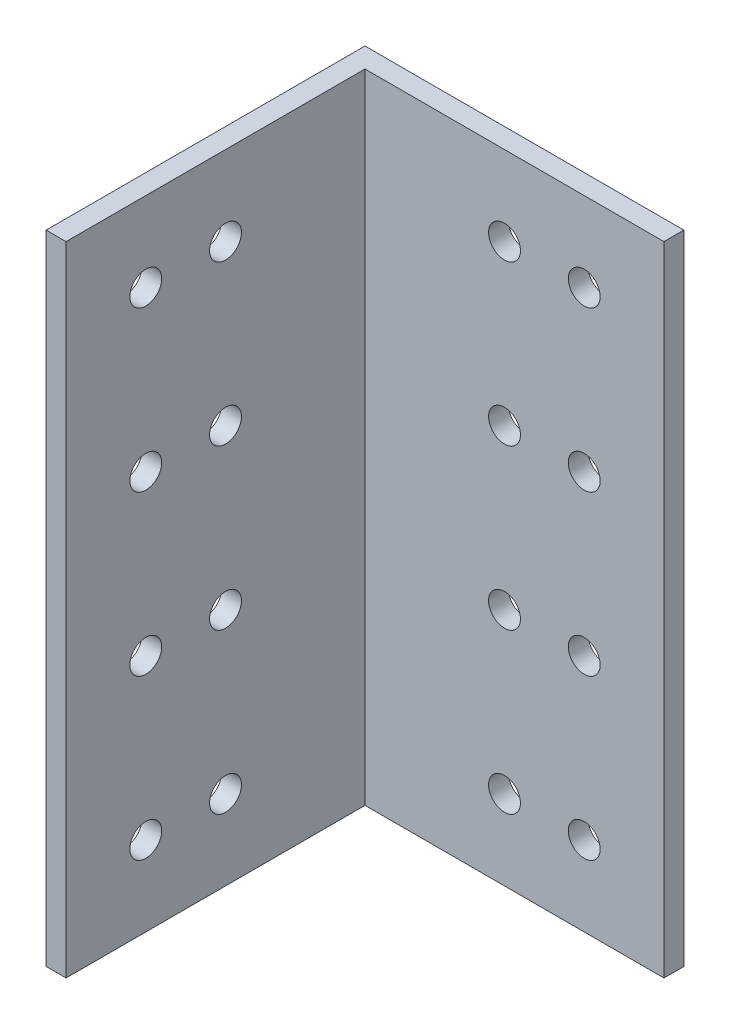
SolidWorks part; units mm, degrees
ref_plane "Front Plane" through (0, 0, 0) normal (0, 0, 1) x (1, 0, 0)
ref_plane "Top Plane" through (0, 0, 0) normal (0, 1, 0) x (1, 0, 0)
ref_plane "Right Plane" through (0, 0, 0) normal (1, 0, 0) x (0, 0, -1)
sketch "Sketch2" plane through (0, 0, 0) normal (0, 1, 0) x (1, 0, 0)
  line L1 (-25.4, -25.4) -> (25.4, -25.4)
  line L2 (-25.4, -25.4) -> (-25.4, 25.4)
  line L3 (-25.4, 25.4) -> (25.4, 25.4)
  line L4 (25.4, -25.4) -> (25.4, 25.4)
  line L5 (-25.4, -25.4) -> (25.4, 25.4) construction
  line L6 (-25.4, 25.4) -> (25.4, -25.4) construction
  line L7 (-22.225, 22.225) -> (25.4, 22.225)
  line L8 (-22.225, 22.225) -> (-22.225, -25.4)
  line L9 (-22.225, -25.4) -> (25.4, -25.4)
  line L10 (25.4, 22.225) -> (25.4, -25.4)
  point P0 (0, 0)
  dimension "D1" = 50.8
  dimension "D2" = 50.8
  dimension "D3" = 47.625
  dimension "D4" = 47.625
extrude "Boss-Extrude1" add sketch "Sketch2" along normal blind 101.6 contours L8 L7 L4 L3 L2 L1 region at (-24.6816, 0, 0)
sketch "Sketch3" plane through (0, 0, -22.225) normal (0, 0, 1) x (1, 0, 0)
  line L0 (-22.225, 0) -> (25.4, 0) construction
  line L2 (25.4, 101.6) -> (25.4, 0) construction
  circle A0 centre (12.7, 88.9) radius 2.54
  circle A1 centre (0, 88.9) radius 2.54
  circle A2 centre (0, 63.5) radius 2.54
  circle A3 centre (12.7, 63.5) radius 2.54
  circle A4 centre (0, 38.1) radius 2.54
  circle A5 centre (12.7, 38.1) radius 2.54
  circle A6 centre (0, 12.7) radius 2.54
  circle A7 centre (12.7, 12.7) radius 2.54
  point P16 (0, 0)
  point P17 (0, 0)
  point P18 (0, 0)
  point P19 (0, 0)
  point P20 (0, 0)
  point P21 (0, 0)
  point P22 (0, 0)
  point P27 (19.8157, 76.9251)
  dimension "D1" = 5.08
  dimension "D7" = 12.7
  dimension "D2" = 12.7
  dimension "D3" = 12.7
  dimension "D4" = 25.4
  dimension "D5" = 25.4
  dimension "D6" = 25.4
extrude "Cut-Extrude1" cut sketch "Sketch3" against normal through all
sketch "Sketch4" plane through (-22.225, 0, 0) normal (1, 0, 0) x (0, 0, -1)
  line L0 (-25.4, 101.6) -> (-25.4, 0) construction
  line L1 (22.225, 0) -> (-25.4, 0) construction
  circle A0 centre (-12.7, 88.9) radius 2.54
  circle A1 centre (0, 88.9) radius 2.54
  circle A2 centre (-12.7, 63.5) radius 2.54
  circle A3 centre (0, 63.5) radius 2.54
  circle A4 centre (-12.7, 38.1) radius 2.54
  circle A5 centre (0, 38.1) radius 2.54
  circle A6 centre (-12.7, 12.7) radius 2.54
  circle A7 centre (0, 12.7) radius 2.54
  point P16 (0, 0)
  point P17 (0, 0)
  point P18 (0, 0)
  point P19 (0, 0)
  point P20 (0, 0)
  point P21 (0, 0)
  dimension "D1" = 5.08
  dimension "D2" = 12.7
  dimension "D3" = 12.7
  dimension "D4" = 12.7
  dimension "D5" = 25.4
  dimension "D6" = 25.4
  dimension "D7" = 25.4
extrude "Cut-Extrude2" cut sketch "Sketch4" against normal through all
